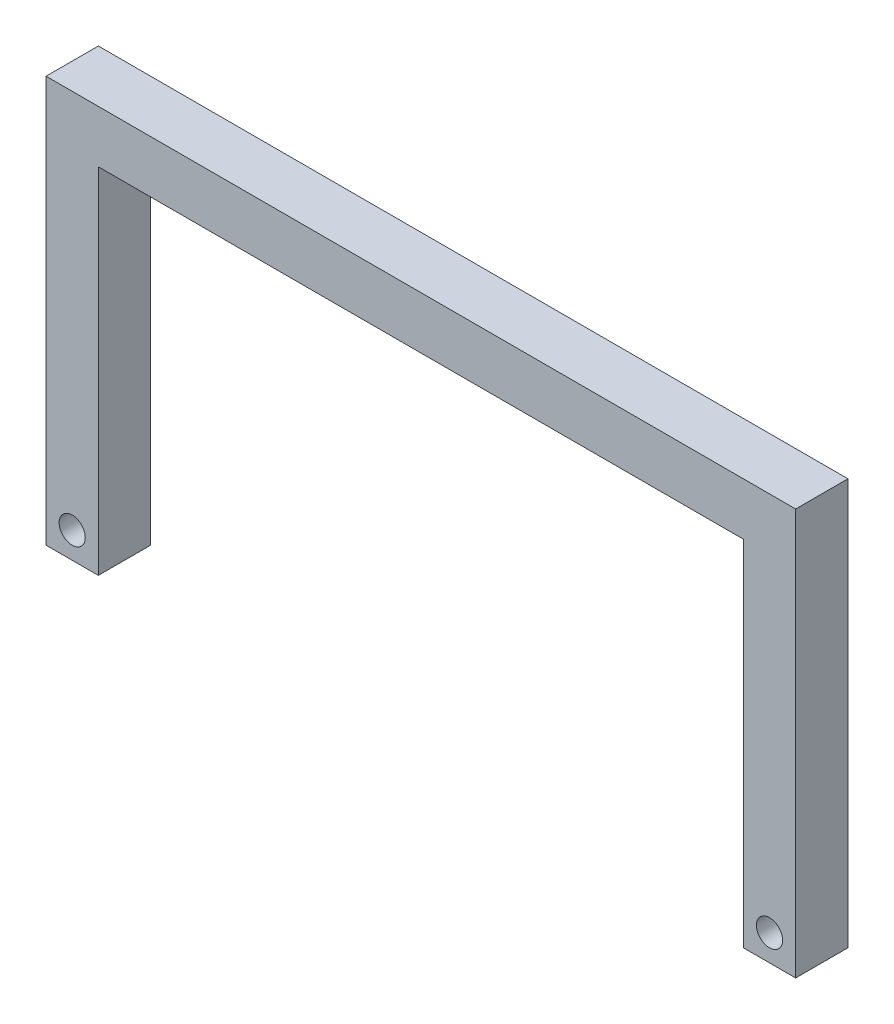
SolidWorks part; units mm, degrees
material "1060 Alloy for 162A"
ref_plane "Front Plane" through (0, 0, 0) normal (0, 0, 1) x (1, 0, 0)
ref_plane "Top Plane" through (0, 0, 0) normal (0, 1, 0) x (1, 0, 0)
ref_plane "Right Plane" through (0, 0, 0) normal (1, 0, 0) x (0, 0, -1)
sketch "Sketch1" plane through (0, 0, 0) normal (0, 0, 1) x (1, 0, 0)
  line L0 (-185, -15) -> (-185, -218)
  line L1 (215, 15) -> (-215, 15)
  line L2 (215, 15) -> (215, -15)
  line L4 (-215, 15) -> (-215, -15)
  line L5 (215, 15) -> (-215, -15) construction
  line L6 (215, -15) -> (-215, 15) construction
  line L8 (-215, 15) -> (-215, -218)
  line L9 (-215, -218) -> (-185, -218)
  line L12 (215, 15) -> (215, -218)
  line L13 (215, -218) -> (185, -218)
  line L15 (185, -15) -> (185, -218)
  line L16 (185, -15) -> (-185, -15)
  circle A0 centre (-200, -203) radius 7.5
  circle A1 centre (200, -203) radius 7.5
  point P0 (0, 0)
  point P8 (215, 15)
  point P14 (0, 0)
  point P17 (-200, -218)
  point P18 (0, 0)
  point P19 (200, -218)
  point P20 (0, 0)
  point P21 (0, 0)
  point P23 (-16.8581, -27.3525)
  point P25 (234.8734, -59.1062)
  point P26 (184.5843, -37.122)
  point P27 (-185, -5.2158)
  point P28 (-92.7438, 15)
  point P29 (-356.1422, 15)
  point P30 (274.8308, 15)
  dimension "D2" = 15
  dimension "D1" = 30
  dimension "D4" = 15
  dimension "D5" = 400
  dimension "D3" = 233
extrude "Boss-Extrude1" add sketch "Sketch1" along normal mid plane 30 contours L16 L15 L13 L12 L2 L1 L4 L8 L9 L0 A1 A0 region at (-189.8907, -116.5, 0)
equation "\"table_height\"=50"
equation "\"A\"= 202"
equation "\"r6\"=400"
equation "\"D5@Sketch1\"=\"r6\""
equation "\"h6\"= 233"
equation "\"D3@Sketch1\"=\"h6\""
